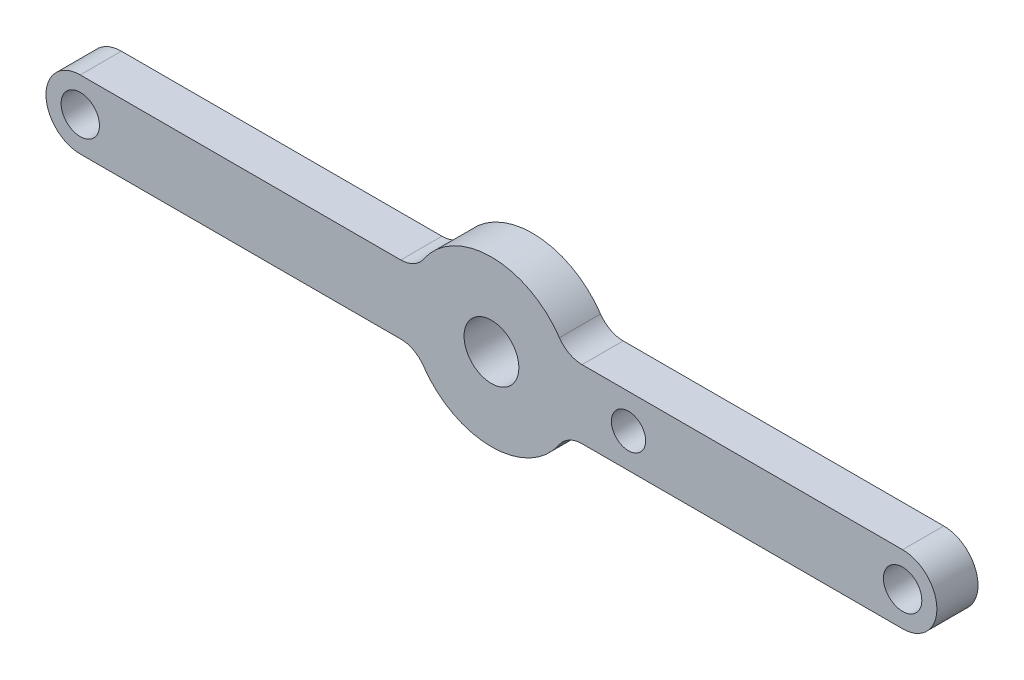
SolidWorks part; units mm, degrees
ref_plane "Plano frontal" through (0, 0, 0) normal (0, 0, 1) x (1, 0, 0)
ref_plane "Plano superior" through (0, 0, 0) normal (0, 1, 0) x (1, 0, 0)
ref_plane "Plano direito" through (0, 0, 0) normal (1, 0, 0) x (0, 0, -1)
sketch "Esboço1" plane through (0, 0, 0) normal (0, 0, 1) x (1, 0, 0)
  line L0 (55, 0) -> (-55, 0) construction
  line L1 (6.6144, 2.5) -> (30, 2.5)
  line L2 (6.6144, -2.5) -> (30, -2.5)
  line L3 (0, -55) -> (0, 55) construction
  line L4 (-6.6144, -2.5) -> (-30, -2.5)
  line L5 (-6.6144, 2.5) -> (-30, 2.5)
  circle A1 centre (0, 0) radius 2
  arc A2 (-4.9608, 3.375) -> (4.9608, 3.375) centre (0, 0) cw
  arc A3 (30, 2.5) -> (32.5, 0) centre (30, 0) cw
  arc A4 (4.9608, 3.375) -> (6.6144, 2.5) centre (6.6144, 4.5) ccw
  arc A7 (4.9608, -3.375) -> (6.6144, -2.5) centre (6.6144, -4.5) cw
  arc A8 (30, -2.5) -> (32.5, 0) centre (30, 0) ccw
  arc A9 (-4.9608, -3.375) -> (4.9608, -3.375) centre (0, 0) ccw
  arc A10 (-30, -2.5) -> (-32.5, 0) centre (-30, 0) cw
  arc A11 (-4.9608, -3.375) -> (-6.6144, -2.5) centre (-6.6144, -4.5) ccw
  arc A14 (-4.9608, 3.375) -> (-6.6144, 2.5) centre (-6.6144, 4.5) cw
  arc A15 (-30, 2.5) -> (-32.5, 0) centre (-30, 0) ccw
  circle A16 centre (10, 0) radius 1.25
  dimension "D1" = 2
  dimension "D2" = 6
  dimension "D3" = 2
  dimension "D7" = 2.5
  dimension "D4" = 2.5
  dimension "D6" = 30
  dimension "D8" = 10
extrude "Ressalto-extrusão1" add sketch "Esboço1" along normal blind 3
sketch "Esboço5" plane through (0, 0, 3) normal (0, 0, 1) x (1, 0, 0)
  point P0 (-30, 0)
ref_axis "Eixo1" through (-30, 0, 3) along (0, 1, 0)
ref_plane "Plano2" through (0, 0, 3) normal (0, 0, 1) x (0, 1, 0)
sketch "Esboço6" plane through (0, 0, 3) normal (0, 0, 1) x (0, 1, 0)
  circle A0 centre (0, 30) radius 1.4
  dimension "D1" = 2.8
extrude "Corte-extrusão1" cut sketch "Esboço6" against normal through all both and the other way through all
mirror "Espelhar1" about plane through (0, 0, 0) normal (1, 0, 0) of "Corte-extrusão1"
